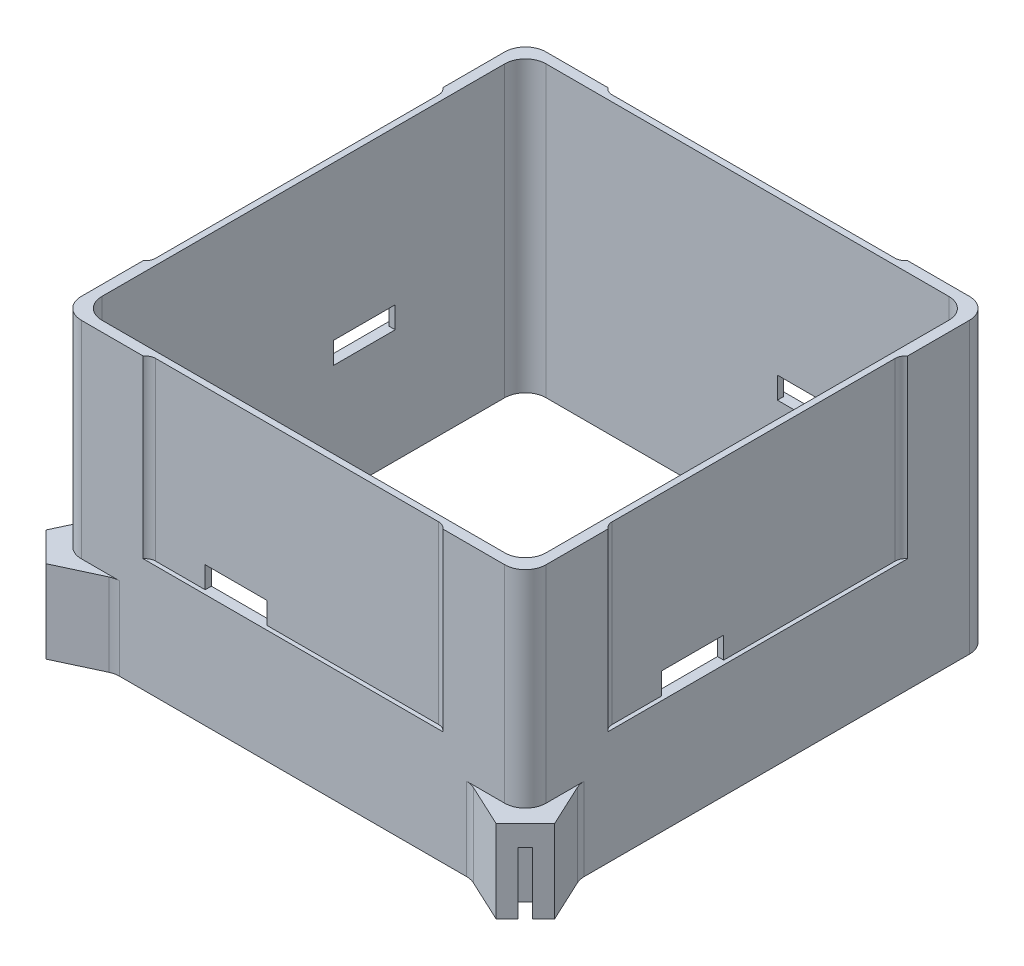
SolidWorks part; units mm, degrees
ref_plane "Front Plane" through (0, 0, 0) normal (0, 0, 1) x (1, 0, 0)
ref_plane "Top Plane" through (0, 0, 0) normal (0, 1, 0) x (1, 0, 0)
ref_plane "Right Plane" through (0, 0, 0) normal (1, 0, 0) x (0, 0, -1)
sketch "Sketch2" plane through (0, 0, 0) normal (0, 1, 0) x (1, 0, 0)
  line L1 (-107.5, -107.5) -> (107.5, -107.5)
  line L2 (-107.5, -107.5) -> (-107.5, 107.5)
  line L3 (-107.5, 107.5) -> (107.5, 107.5)
  line L4 (107.5, -107.5) -> (107.5, 107.5)
  line L5 (-107.5, -107.5) -> (107.5, 107.5) construction
  line L6 (-107.5, 107.5) -> (107.5, -107.5) construction
  line L7 (-112.5, -112.5) -> (112.5, -112.5)
  line L8 (-112.5, -112.5) -> (-112.5, 112.5)
  line L9 (-112.5, 112.5) -> (112.5, 112.5)
  line L10 (112.5, -112.5) -> (112.5, 112.5)
  line L11 (-112.5, -112.5) -> (112.5, 112.5) construction
  line L12 (-112.5, 112.5) -> (112.5, -112.5) construction
  point P0 (0, 0)
  point P6 (0, 0)
  dimension "D1" = 215
  dimension "D2" = 215
  dimension "D3" = 5
  dimension "D4" = 5
extrude "Boss-Extrude1" add sketch "Sketch2" along normal blind 140
sketch "Sketch3" plane through (0, 0, 112.5) normal (0, 0, 1) x (1, 0, 0)
  line L0 (-112.5, 140) -> (-112.5, 0) construction
  line L1 (-44.5, 65.5) -> (-14.5, 65.5)
  line L2 (-44.5, 65.5) -> (-44.5, 55)
  line L3 (-44.5, 55) -> (-14.5, 55)
  line L4 (-14.5, 65.5) -> (-14.5, 55)
  line L5 (-44.5, 65.5) -> (-14.5, 55) construction
  line L6 (-44.5, 55) -> (-14.5, 65.5) construction
  line L7 (-112.5, 0) -> (112.5, 0) construction
  point P0 (-29.5, 60.25)
  dimension "D1" = 68
  dimension "D2" = 55
  dimension "D3" = 10.5
  dimension "D4" = 30
extrude "Cut-Extrude1" cut sketch "Sketch3" against normal up to next
sketch "Sketch4" plane through (0, 0, -112.5) normal (0, 0, -1) x (-1, 0, 0)
  line L0 (-112.5, 140) -> (-112.5, 0) construction
  line L1 (-44.5, 65.5) -> (-14.5, 65.5)
  line L2 (-44.5, 65.5) -> (-44.5, 55)
  line L3 (-44.5, 55) -> (-14.5, 55)
  line L4 (-14.5, 65.5) -> (-14.5, 55)
  line L5 (-44.5, 65.5) -> (-14.5, 55) construction
  line L6 (-44.5, 55) -> (-14.5, 65.5) construction
  line L7 (55, 0) -> (-55, 0) construction
  point P0 (-29.5, 60.25)
  dimension "D1" = 68
  dimension "D2" = 55
  dimension "D3" = 10.5
  dimension "D4" = 30
extrude "Cut-Extrude2" cut sketch "Sketch4" against normal up to next
sketch "Sketch5" plane through (0, 140, 0) normal (0, 1, 0) x (1, 0, 0)
  line L0 (-1000, 0) -> (49000, 0) construction
  circle A0 centre (-107.5, 107.5) radius 1.25
  circle A1 centre (107.5, 107.5) radius 2.5
  circle A2 centre (107.5, -107.5) radius 2.5
  circle A3 centre (-107.5, -107.5) radius 1.25
  dimension "D1" = 2.5
  dimension "D2" = 5
sketch "Sketch6" plane through (0, 0, 0) normal (0, 1, 0) x (1, 0, 0)
  line L0 (-112.5, -86.2185) -> (-123.1066, -108.9645)
  line L1 (-112.5, 112.5) -> (-112.5, -112.5) construction
  line L2 (-123.1066, -108.9645) -> (-108.9645, -123.1066)
  line L3 (-108.9645, -123.1066) -> (-86.2185, -112.5)
  line L4 (-112.5, -112.5) -> (112.5, -112.5) construction
  line L5 (-116, -116) -> (-35471.3391, -35471.3391) construction
  line L6 (0, -1000) -> (0, 49000) construction
  line L7 (112.5, -86.2185) -> (112.5, -112.5)
  line L8 (112.5, -86.2185) -> (123.1066, -108.9645)
  line L9 (123.1066, -108.9645) -> (108.9645, -123.1066)
  line L10 (-112.5, -86.2185) -> (-112.5, -112.5)
  line L11 (-112.5, -112.5) -> (-86.2185, -112.5)
  line L12 (108.9645, -123.1066) -> (86.2185, -112.5)
  line L13 (112.5, -112.5) -> (86.2185, -112.5)
  point P4 (-116.0355, -116.0355)
  dimension "D1" = 45
  dimension "D2" = 5
  dimension "D3" = 110
  dimension "D4" = 20
  dimension "D5" = 0
  dimension "D6" = 135
  dimension "D7" = 110
extrude "Boss-Extrude2" add sketch "Sketch6" along normal blind 40
sketch "Sketch7" plane through (0, 0, 0) normal (0, 1, 0) x (1, 0, 0)
  line L0 (112.5, 112.5) -> (-112.5, 112.5) construction
  line L3 (-10, 120) -> (10, 120)
  line L5 (-10, 120) -> (-26.0838, 112.5)
  line L8 (10, 120) -> (26.0838, 112.5)
  line L9 (-26.0838, 112.5) -> (26.0838, 112.5)
  point P0 (0, 120)
  dimension "D1" = 20
  dimension "D2" = 7.5
  dimension "D3" = 25
  dimension "D4" = 25
extrude "Boss-Extrude3" add sketch "Sketch7" along normal blind 40
sketch "Sketch8" plane through (0, 0, 0) normal (0, -1, 0) x (1, 0, 0)
  line L5 (-114.2678, 117.8033) -> (-117.8033, 114.2678)
  line L6 (-123.1066, 108.9645) -> (-108.9645, 123.1066) construction
  line L10 (0, -1000) -> (0, 49000) construction
  line L15 (-110.7322, 114.2678) -> (-107.1967, 117.8033)
  line L16 (-107.1967, 117.8033) -> (-103.6612, 114.2678)
  line L17 (-103.6612, 114.2678) -> (-114.2678, 103.6612)
  line L18 (-114.2678, 103.6612) -> (-117.8033, 107.1967)
  line L19 (-117.8033, 107.1967) -> (-114.2678, 110.7322)
  line L20 (-114.2678, 110.7322) -> (-117.8033, 114.2678)
  line L21 (-110.7322, 114.2678) -> (-114.2678, 117.8033)
  line L22 (110.7322, 114.2678) -> (107.1967, 117.8033)
  line L23 (107.1967, 117.8033) -> (103.6612, 114.2678)
  line L24 (103.6612, 114.2678) -> (114.2678, 103.6612)
  line L25 (114.2678, 103.6612) -> (117.8033, 107.1967)
  line L26 (117.8033, 107.1967) -> (114.2678, 110.7322)
  line L27 (114.2678, 110.7322) -> (117.8033, 114.2678)
  line L28 (114.2678, 117.8033) -> (117.8033, 114.2678)
  line L29 (110.7322, 114.2678) -> (114.2678, 117.8033)
  line L30 (-2.5, -120) -> (2.5, -120)
  line L31 (10, -120) -> (-10, -120) construction
  line L32 (2.5, -120) -> (2.5, -115)
  line L33 (2.5, -115) -> (7.5, -115)
  line L34 (7.5, -115) -> (7.5, -110)
  line L35 (7.5, -110) -> (-7.5, -110)
  line L36 (-7.5, -110) -> (-7.5, -115)
  line L37 (-7.5, -115) -> (-2.5, -115)
  line L38 (-2.5, -115) -> (-2.5, -120)
  point P4 (0, -120)
  point P11 (-116.0355, 116.0355)
  line M12 (123.1066, 108.9645) -> (108.9645, 123.1066)
  line M16 (-108.9645, 123.1066) -> (-123.1066, 108.9645)
  line M21 (-10, -120) -> (10, -120)
  dimension "D1" = 5
  dimension "D2" = 5
  dimension "D3" = 5
  dimension "D4" = 5
  dimension "D5" = 5
  dimension "D6" = 5
  dimension "D7" = 5
extrude "Cut-Extrude4" cut sketch "Sketch8" against normal blind 30 contours L15 L21 L20 L19 L18 L17 L16 M16 | L29 L22 L23 L24 L25 L26 L27 M12 | L10 L30 L32 L33 L34 L35 | L10 L35 L36 L37 L38 M21 region at (-111.6161, 0, 111.6161) region at (-3.125, 0, -113.75) region at (3.125, 0, -113.75) region at (111.6161, 0, 111.6161)
fillet "Fillet1" radius 10 14 edges at (-86.2185, 20, 112.5) (-112.5, 20, 86.2185) (-26.0838, 20, -112.5) (26.0838, 20, -112.5) (112.5, 20, 86.2185) (86.2185, 20, 112.5) (-112.5, 70, -112.5) (112.5, 70, -112.5) (112.5, 90, 112.5) (-112.5, 90, 112.5) (-107.5, 70, 107.5) (107.5, 70, 107.5) (107.5, 70, -107.5) (-107.5, 70, -107.5)
sketch "Sketch9" plane through (0, 0, 0) normal (0, 1, 0) x (1, 0, 0)
  line L0 (-117.0355, -117.0355) -> (35238.3035, 35238.3035) construction
  circle A0 centre (0, 0) radius 390
  dimension "D1" = 780
sketch "Sketch10" plane through (112.5, 0, 0) normal (1, 0, 0) x (0, 0, -1)
  line L0 (390, 0) -> (-390, 0) construction
  line L1 (-44.5, 65.5) -> (-14.5, 65.5)
  line L2 (-44.5, 65.5) -> (-44.5, 55)
  line L3 (-44.5, 55) -> (-14.5, 55)
  line L4 (-14.5, 65.5) -> (-14.5, 55)
  dimension "D1" = 55
  dimension "D2" = 10.5
  dimension "D3" = 30
  dimension "D4" = 68
extrude "Cut-Extrude5" cut sketch "Sketch10" against normal up to surface (5 mm away) up to face at (107.5, 70, 0)
sketch "Sketch11" plane through (-112.5, 0, 0) normal (-1, 0, 0) x (0, 0, 1)
  line L0 (141538.3918, 0) -> (-176659.6598, 0) construction
  line L1 (-44.5, 65.5) -> (-14.5, 65.5)
  line L2 (-44.5, 65.5) -> (-44.5, 55)
  line L3 (-44.5, 55) -> (-14.5, 55)
  line L4 (-14.5, 65.5) -> (-14.5, 55)
  dimension "D1" = 55
  dimension "D2" = 68
  dimension "D3" = 30
  dimension "D4" = 10.5
extrude "Cut-Extrude7" cut sketch "Sketch11" against normal up to surface (5 mm away) contours L4 L1 L2 L3 region at (-112.5, 60.25, -29.5) up to face at (-107.5, 70, 0)
sketch "Sketch12" plane through (0, 140, 0) normal (0, 1, 0) x (1, 0, 0)
  line L0 (-112.5, 102.5) -> (-112.5, -102.5) construction
  line L1 (-112.5, 72.5) -> (-110.5, 72.5)
  line L2 (-112.5, 72.5) -> (-112.5, -72.5)
  line L3 (-112.5, -72.5) -> (-110.5, -72.5)
  line L4 (-110.5, 72.5) -> (-110.5, -72.5)
  line L5 (-102.5, -112.5) -> (102.5, -112.5) construction
  line L6 (102.5, 112.5) -> (-102.5, 112.5) construction
  line L19 (72.5, 112.5) -> (-72.5, 112.5)
  line L20 (72.5, 112.5) -> (72.5, 110.5)
  line L21 (72.5, 110.5) -> (-72.5, 110.5)
  line L22 (-72.5, 112.5) -> (-72.5, 110.5)
  line L23 (112.5, -72.5) -> (112.5, 72.5)
  line L24 (112.5, -72.5) -> (110.5, -72.5)
  line L25 (110.5, -72.5) -> (110.5, 72.5)
  line L26 (112.5, 72.5) -> (110.5, 72.5)
  line L27 (-72.5, -112.5) -> (72.5, -112.5)
  line L28 (-72.5, -112.5) -> (-72.5, -110.5)
  line L29 (-72.5, -110.5) -> (72.5, -110.5)
  line L30 (72.5, -112.5) -> (72.5, -110.5)
  point P25 (2.5, 0)
  point P26 (0, 0)
  line M5 (102.5, 112.5) -> (-102.5, 112.5)
  line M7 (-112.5, 102.5) -> (-112.5, -102.5)
  line M9 (-102.5, -112.5) -> (102.5, -112.5)
  line M11 (112.5, -102.5) -> (112.5, 102.5)
  dimension "D1" = 2
  dimension "D2" = 40
  dimension "D3" = 40
  dimension "D4" = 4
extrude "Cut-Extrude8" cut sketch "Sketch12" against normal up to surface (85 mm away) contours L4 L1 L3 M7 | L28 L30 L29 M9 | L20 L22 L21 M5 | L24 L26 L25 M11 region at (-111.5, 140, 0) region at (0, 140, -111.5) region at (111.5, 140, 0) region at (0, 140, 111.5) up to face at (110, 55, 29.5)
fillet "Fillet2" radius 5 8 edges at (-72.5, 97.5, -110.5) (72.5, 97.5, -110.5) (110.5, 97.5, -72.5) (110.5, 97.5, 72.5) (72.5, 97.5, 110.5) (-72.5, 97.5, 110.5) (-110.5, 97.5, 72.5) (-110.5, 97.5, -72.5)
